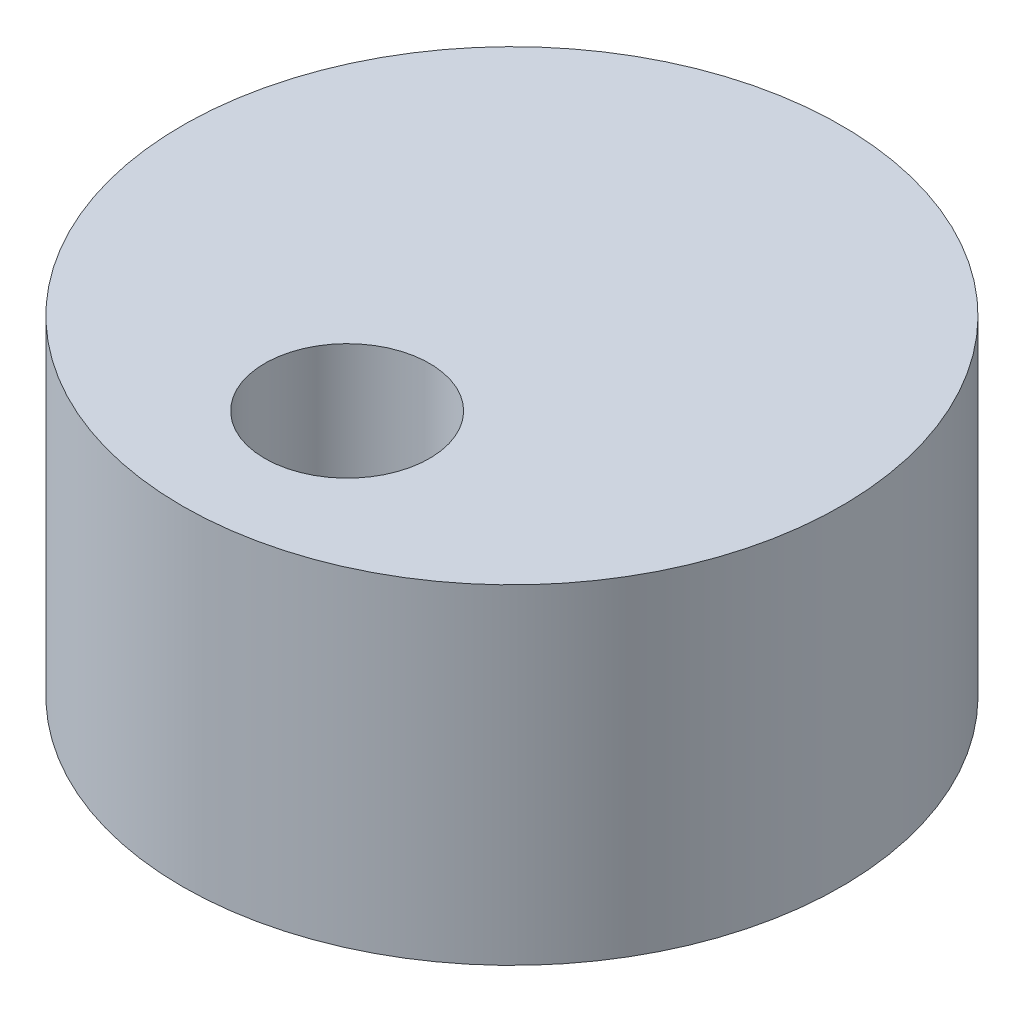
SolidWorks part; units mm, degrees
ref_plane "Front Plane" through (0, 0, 0) normal (0, 0, 1) x (1, 0, 0)
ref_plane "Top Plane" through (0, 0, 0) normal (0, 1, 0) x (1, 0, 0)
ref_plane "Right Plane" through (0, 0, 0) normal (1, 0, 0) x (0, 0, -1)
sketch "Sketch1" plane through (0, 0, 0) normal (0, 1, 0) x (1, 0, 0)
  line L0 (0, -3.175) -> (0, 0) construction
  circle A0 centre (0, 0) radius 6.35
  circle A1 centre (0, -3.175) radius 1.5875
  dimension "D1" = 12.7
  dimension "D2" = 3.175
  dimension "D3" = 3.175
extrude "Boss-Extrude1" add sketch "Sketch1" along normal blind 6.35
equation "\"R\"= 1.5in'radius of rotor"
equation "\"E\"= .125in'eccentricity"
equation "\"R_r\"= .125in'radius of roller"
equation "\"N\"= 9'number of rollers"
equation "\"R_o\"= .125in'output disk pin diameter"
equation "\"D3@Sketch1\"=\"E\""
